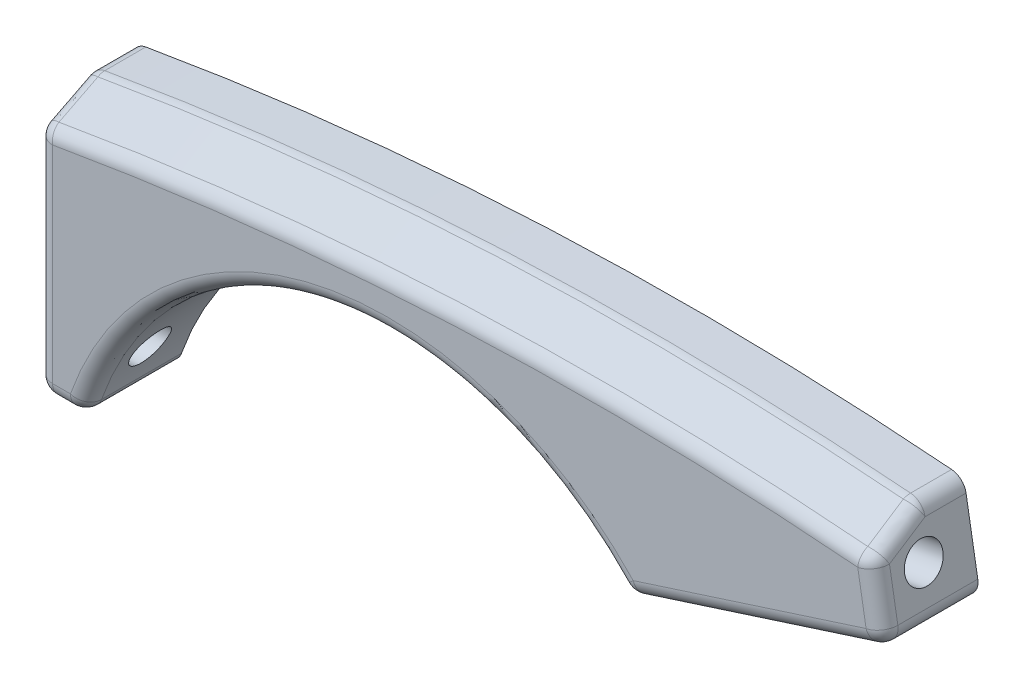
SolidWorks part; units mm, degrees
ref_plane "Front Plane" through (0, 0, 0) normal (0, 0, 1) x (1, 0, 0)
ref_plane "Top Plane" through (0, 0, 0) normal (0, 1, 0) x (1, 0, 0)
ref_plane "Right Plane" through (0, 0, 0) normal (1, 0, 0) x (0, 0, -1)
sketch "Sketch1" plane through (0, 0, 0) normal (0, 0, 1) x (1, 0, 0)
  line L0 (0, 0) -> (0, -25.4)
  line L2 (82.55, 3.81) -> (84.1536, -5.579)
  line L3 (0, -25.4) -> (4.5043, -25.4)
  line L4 (244.467, -237.1135) -> (141.8498, -254.6403) construction
  line L5 (84.1536, -5.579) -> (58.7536, -13.751)
  arc A1 (0, 0) -> (82.55, 3.81) centre (55.7888, -312.5602) cw
  circle A2 centre (34.925, -34.925) radius 31.877 construction
  arc A3 (4.5043, -25.4) -> (58.7536, -13.751) centre (34.925, -34.925) cw
  point P5 (83.7908, -5.6459)
  point P9 (0, 0)
  point P10 (0, 0)
  point P11 (-3.175, -10.7802)
  point P12 (4.5043, -25.4)
  point P21 (-14.8896, -5.0533)
  dimension "D1" = 31.877
  dimension "D2" = 317.5
  dimension "D3" = 82.55
  dimension "D4" = 25.4
  dimension "D5" = 9.525
  dimension "D6" = 25.4
  dimension "D7" = 3.81
extrude "Boss-Extrude1" add sketch "Sketch1" along normal blind 9.525
chamfer "Chamfer1" distance 5.08 distance2 2.54 1 edges at (41.1505, 4.6022, 9.525) first distance on face at (41.2128, 3.2536, 4.7625)
sketch "Sketch2" plane through (80.8424, 13.8077, 0) normal (0.9857, 0.1684, 0) x (0, 0, -1)
  circle A0 centre (-4.7625, -14.7218) radius 1.905
  arc A1 (-6.8625, -14.7218) -> (-2.6625, -14.7218) centre (-4.7625, -14.7218) ccw construction
  dimension "D1" = 3.81
extrude "Cut-Extrude1" cut sketch "Sketch2" against normal blind 12.7
sketch "Sketch3" plane through (0, 0, 0) normal (-1, 0, 0) x (0, 0, 1)
  line L0 (4.7625, -10.9951) -> (4.7625, -0.1613) construction
  line L1 (-94.2444, -75.6464) -> (8.2538, -29.792) construction
  line L3 (4.7625, -20.5201) -> (4.7625, -31.3538) construction
  line L5 (0, 0) -> (0, -25.4) construction
  circle A0 centre (4.7625, -10.9951) radius 1.905
  circle A1 centre (4.7625, -20.5201) radius 1.905
  spline S0 degree 3 poles (9.525, -2.5805) (7.8317, -1.7202) (6.1384, -0.8601) (4.445, 0) knots 0 0 0 0 0.005698 0.005698 0.005698 0.005698 construction
  point P6 (4.7625, -0.1612)
  point P9 (4.7625, -31.3538)
  point P12 (1.801, -4.9985)
  dimension "D3" = 3.81
  dimension "D1" = 9.525
  dimension "D2" = 4.7625
extrude "Cut-Extrude2" cut sketch "Sketch3" against normal blind 9.525
fillet "Fillet1" radius 1.5875 15 edges at (71.4536, -9.665, 9.525) (28.2326, -3.7584, 9.525) (2.2522, -25.4, 9.525) (0, -13.9902, 9.525) (83.5727, -2.1781, 9.525) (41.37, 2.0696, 9.525) (41.1505, 4.6022, 4.445) (58.7536, -13.751, 4.7625) (4.5043, -25.4, 4.7625) (0, 0, 2.2225) (0, -25.4, 4.7625) (84.1536, -5.579, 4.7625) (82.55, 3.81, 2.2225)
